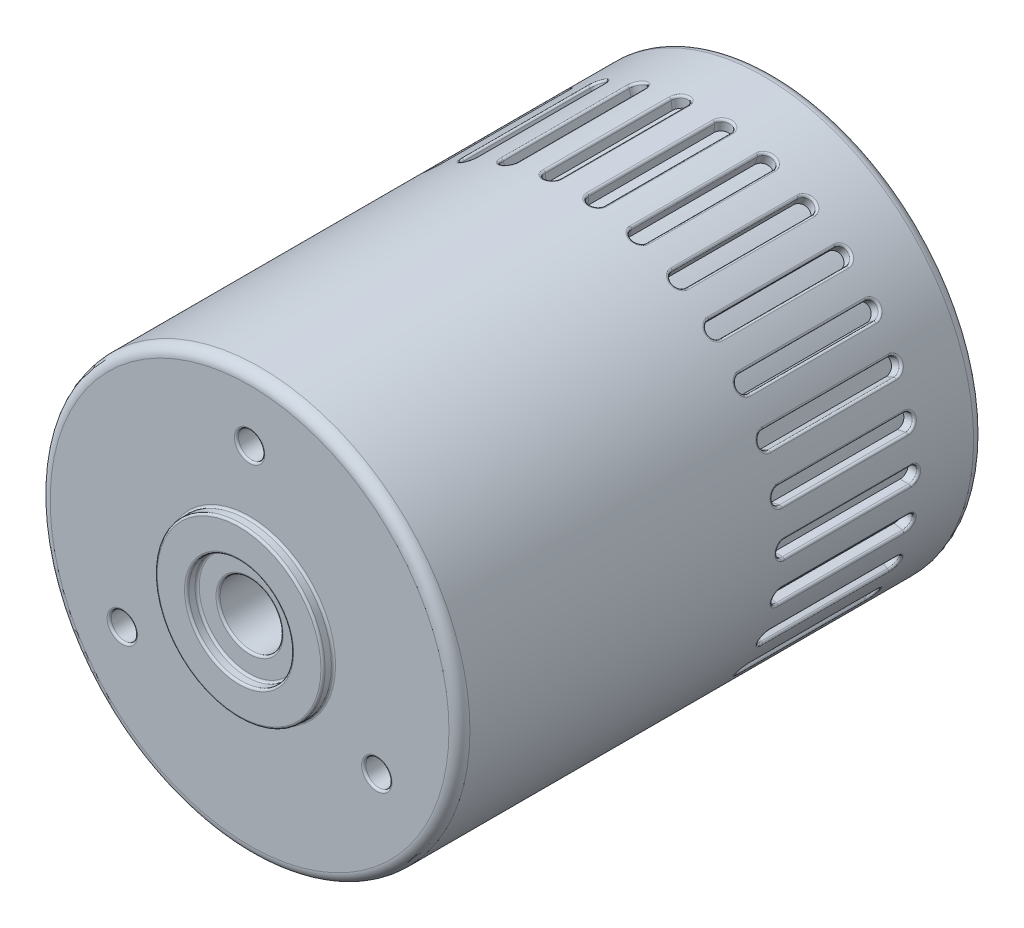
SolidWorks part; units mm, degrees
ref_plane "Front Plane" through (0, 0, 0) normal (0, 0, 1) x (1, 0, 0)
ref_plane "Top Plane" through (0, 0, 0) normal (0, 1, 0) x (1, 0, 0)
ref_plane "Right Plane" through (0, 0, 0) normal (1, 0, 0) x (0, 0, -1)
sketch "Sketch1" plane through (0, 0, 0) normal (0, 0, 1) x (1, 0, 0)
  circle A0 centre (0, 0) radius 10
  circle A1 centre (0, 0) radius 4 construction
  circle A2 centre (0, 0) radius 2.5 construction
  circle A3 centre (0, 0) radius 1.5 construction
  dimension "D1" = 20
  dimension "D2" = 3
  dimension "D3" = 5
  dimension "D4" = 8
extrude "Boss-Extrude1" add sketch "Sketch1" against normal blind 25
sketch "Sketch2" plane through (0, 0, 0) normal (0, 0, 1) x (1, 0, 0)
  circle A1 centre (0, 0) radius 2.5 construction
  circle A2 centre (0, 0) radius 4 construction
  circle A3 centre (0, 0) radius 2.5
  circle A4 centre (0, 0) radius 4
extrude "Boss-Extrude2" add sketch "Sketch2" along normal blind 0.5
sketch "Sketch3" plane through (0, 0, -25) normal (0, 0, -1) x (-1, 0, 0)
  circle A0 centre (0, 0) radius 1.5
  dimension "D1" = 3
extrude "Boss-Extrude3" add sketch "Sketch3" along normal blind 0.5
sketch "Sketch4" plane through (0, 0, 0) normal (1, 0, 0) x (0, 0, -1)
  line L0 (15.5, 0) -> (21.5, 0) construction
  line L1 (15.5, 0.375) -> (21.5, 0.375)
  line L2 (15.5, -0.375) -> (21.5, -0.375)
  arc A0 (15.5, 0.375) -> (15.5, -0.375) centre (15.5, 0) ccw
  arc A1 (21.5, -0.375) -> (21.5, 0.375) centre (21.5, 0) ccw
  point P3 (18.5, 0)
  dimension "D3" = 0.75
  dimension "D1" = 18.5
  dimension "D2" = 6
extrude "Cut-Extrude1" cut sketch "Sketch4" against normal offset from surface (20.507 mm away) 0.5 from offset 30
fillet "Fillet1" radius 0.1 4 edges at (9.9999, 0.0433, -21.8725) (9.993, -0.375, -18.5) (9.9999, -0.0433, -15.1275) (9.993, 0.375, -18.5)
pattern_circular "CirPattern1" count 30 over 360 about axis through (0, 0, -25) along (0, 0, 1) of "Cut-Extrude1", "Fillet1"
sketch "Sketch5" plane through (0, 0, 0) normal (0, 0, 1) x (1, 0, 0)
  circle A0 centre (0, 0) radius 1.5 construction
  circle A1 centre (0, 0) radius 1.5
extrude "Cut-Extrude2" cut sketch "Sketch5" against normal blind 5
fillet "Fillet2" radius 0.5 2 edges at (10, 0, 0) (10, 0, -25)
sketch "Sketch6" plane through (0, 0, 0) normal (0, 0, 1) x (1, 0, 0)
  circle A0 centre (0, 7) radius 0.625
  circle A1 centre (6.0622, -3.5) radius 0.625
  circle A2 centre (-6.0622, -3.5) radius 0.625
  point P10 (0, 0)
  dimension "D2" = 1.25
  dimension "D1" = 7
  dimension "D3" = 3
extrude "Cut-Extrude3" cut sketch "Sketch6" against normal blind 5
fillet "Fillet3" radius 0.1 9 edges at (2.5, 0, 0) (1.5, 0, 0) (2.5, 0, 0.5) (4, 0, 0) (4, 0, 0.5) (0.625, 7, 0) (0.625, 7, -5) (6.6872, -3.5, 0) (-5.4372, -3.5, 0)
fillet "Fillet4" radius 0.1 2 edges at (-1.5, 0, -25) (-1.5, 0, -25.5)
